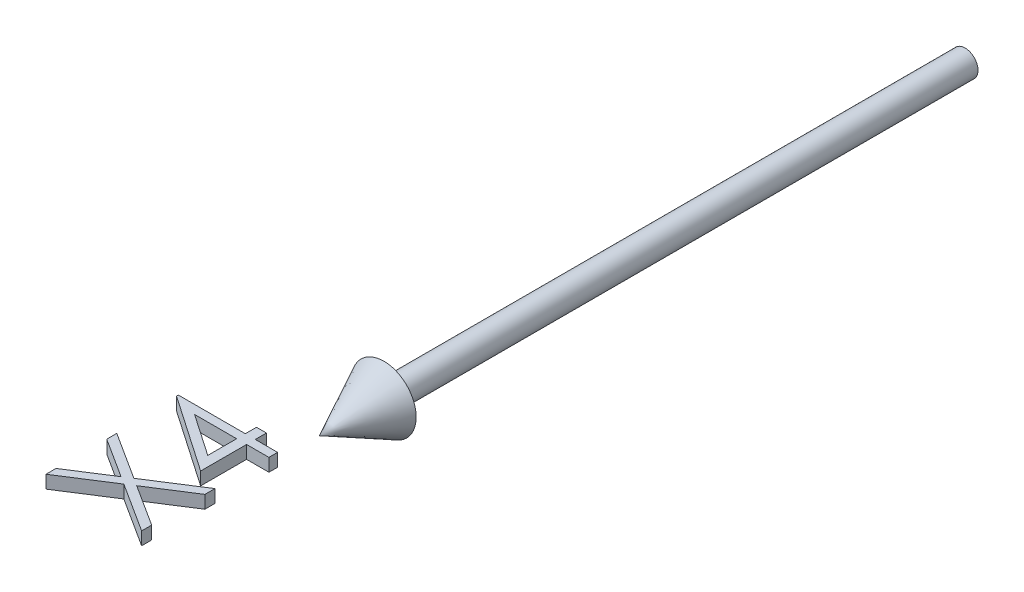
SolidWorks part; units mm, degrees
ref_plane "Front Plane" through (0, 0, 0) normal (0, 0, 1) x (1, 0, 0)
ref_plane "Top Plane" through (0, 0, 0) normal (0, 1, 0) x (1, 0, 0)
ref_plane "Right Plane" through (0, 0, 0) normal (1, 0, 0) x (0, 0, -1)
sketch "Sketch2" plane through (0, 0, 0) normal (0, 1, 0) x (1, 0, 0)
  line L0 (0, 41.95) -> (0, -114.4521) construction
  line L1 (-36.8894, 0) -> (41.4965, 0) construction
  line L2 (0, -100) -> (5, -90)
  line L3 (5, -90) -> (2, -90)
  line L4 (2, -90) -> (2, 0)
  line L5 (2, 0) -> (0, 0)
  line L6 (0, 0) -> (0, -100)
  dimension "D1" = 100
  dimension "D2" = 2
  dimension "D3" = 10
  dimension "D4" = 5
revolve "Revolve1" add sketch "Sketch2" angle 360 about L0
sketch "Sketch3" plane through (0, 0, 0) normal (0, 1, 0) x (1, 0, 0)
  line L0 (0, -103.9528) -> (0, -147.2622) construction
  line L1 (-18.6107, -118.3811) -> (18.3141, -118.3811) construction
  text T0 "X4\r\n" font "Century Gothic" height 15
extrude "Boss-Extrude1" add sketch "Sketch3" against normal blind 1 and the other way blind 1 separate body
equation "\"frame_arrow_length\"=100"
equation "\"D1@Sketch2\"=\"frame_arrow_length\""
equation "\"frame_arrow_odA\"=4"
equation "\"D2@Sketch2\"=\"frame_arrow_odA\"/2"
equation "\"frame_arrow_head_od\"=5"
equation "\"D4@Sketch2\"=\"frame_arrow_head_od\""
equation "\"frame_arrow_head_length\"=10"
equation "\"D3@Sketch2\"=\"frame_arrow_head_length\""
equation "\"tvarobot_theta1\"=30"
equation "\"link0_ringA_odA\"= 40"
equation "\"link0_ringA_odB\"= 25"
equation "\"link0_ringA_id\"= 20"
equation "\"link0_ringA_thickness\"= (\"link0_ringA_odB\" - \"link0_ringA_id\")/2"
equation "\"link0_ringA_height\"= 3"
equation "\"link0_ringA_heightA\"= 1.5"
equation "\"link0_ringA_heightB\"=\"link0_ringA_height\"-\"link0_ringA_heightA\""
equation "\"link0_ringB_odA\"= 40"
equation "\"link0_ringB_odB\"= 29"
equation "\"link0_ringB_id\"= \"link0_shaftA_bearing_id\"+1"
equation "\"link0_ringB_thickness\"= (\"link0_ringB_odB\" - \"link0_ringB_id\")/2"
equation "\"link0_ringB_height\"= 3"
equation "\"link0_ringB_heightA\"= 1.5"
equation "\"link0_ringB_heightB\"=\"link0_ringB_height\"-\"link0_ringB_heightA\""
equation "\"link0_shaftA_bearing_od\"=27"
equation "\"link0_shaftA_bearing_id\"=20"
equation "\"link0_shaftA_thrust_bearing_od\"=35"
equation "\"link0_shaftA_thrust_bearing_id\"=20.04"
equation "\"link0_shaftA_retaining_ring_id\"=18.5"
equation "\"link0_shaftA_retaining_ring_groove_width\"=1.5"
equation "\"link0_shaftA_spline_length\"=8.0"
equation "\"link0_shaftA_spline_depth\"=1.0"
equation "\"link0_shaftA_spline_width\"=4.0"
equation "\"link0_shaftA_odA\"=\"link0_shaftA_bearing_id\""
equation "\"link0_shaftA_odB\"=35"
equation "\"link0_shaftA_odC\"=\"link0_shaftA_bearing_id\""
equation "\"link0_shaftA_odD\"=\"link0_shaftA_odC\"-2*\"link0_shaftA_spline_depth\""
equation "\"link0_shaftA_odE\"=\"link0_shaftA_bearing_id\""
equation "\"link0_shaftA_odF\"=\"link0_shaftA_odE\"-2*\"link0_shaftA_spline_depth\""
equation "\"link0_shaftA_idA\"=10"
equation "\"link0_shaftA_idB\"=6"
equation "\"link0_shaftA_length\"=39.5"
equation "\"link0_shaftA_lengthA\"=8.0"
equation "\"link0_shaftA_lengthB\"=12.0"
equation "\"link0_shaftA_lengthC\"=35.0"
equation "\"link0_shaftA_lengthD\"=39.0"
equation "\"link0_shaftA_lengthE\"=\"link0_shaftA_length\"-\"link0_shaftA_lengthD\""
equation "\"link0_shaftA_offsetX\"=11"
equation "\"link0_shaftA_offsetY\"=0"
equation "\"link0_shaftA_bolt_pattern_dia\"=14"
equation "\"link0_motor_center_dist\"=26"
equation "\"link0_46t_pulley_spline_length\"=8"
equation "\"link0_46t_pulley_spline_depth\"=\"link0_shaftA_spline_depth\"*1.025"
equation "\"link0_46t_pulley_spline_width\"=\"link0_shaftA_spline_width\"*1.05"
equation "\"link0_46t_pulley_idA\"=\"link0_shaftA_bearing_id\"*1.025"
equation "\"link0_46t_pulley_idB\"=\"link0_46t_pulley_idA\"-2*\"link0_46t_pulley_spline_depth\""
equation "\"link0_shaftB_spline_length\"=10"
equation "\"link0_shaftB_spline_depth\"=1.0"
equation "\"link0_shaftB_spline_width\"=1.25"
equation "\"link0_shaftB_length\"=7"
equation "\"link0_shaftB_lengthA\"=1.5"
equation "\"link0_shaftB_lengthB\"=2.75"
equation "\"link0_shaftB_odA\"=32"
equation "\"link0_shaftB_odB\"=22"
equation "\"link0_shaftB_odC\"=20"
equation "\"link0_shaftB_idA\"=10"
equation "\"link0_shaftB_bolt_diameter\"=19"
equation "\"link0_shaftB_bearing_od\"=27"
equation "\"link0_shaftB_bearing_id\"=20"
equation "\"link0_motor_length\"=46.5"
equation "\"link0_motor_width\"=28.5"
equation "\"link0_motor_height\"=34"
equation "\"link0_motor_offset\"=8"
equation "\"link0_shellA_thickness\"=2.5"
equation "\"link0_shellB_thickness\"=\"link0_shellA_thickness\""
equation "\"link0_plateA_shellA_height\"=48"
equation "\"link0_shellA_width\" =\"link0_plateA_width\""
equation "\"link0_shellA_height\" = \"link0_plateA_shellA_height\"-\"link0_plateA_height\""
equation "\"link0_shellA_length\" = \"link0_plateA_lengthB\" "
equation "\"link0_shellB_length\"=\"link0_shellA_length\""
equation "\"link0_shellA_radius\" = 0.375*25.4"
equation "\"link0_shellA_radiusA\"= \"link0_plateA_radiusA\""
equation "\"link0_shellA_radiusB\"= \"link0_plateA_radiusB\""
equation "\"link0_shellA_radiusC\"= 3"
equation "\"link0_postA_height\"=7"
equation "\"link0_postA_width\"=16"
equation "\"link0_postA_length\"=20"
equation "\"link0_postA_posX\"=22"
equation "\"link0_postA_posY\"=17.5"
equation "\"link0_postA_pocket_width\"=6.0"
equation "\"link0_postA_pocket_length\"=2.5"
equation "\"link0_postA_pocket_depth\"=9"
equation "\"link0_postA_pocket_posZ\"=10"
equation "\"link0_postB_height\"=7"
equation "\"link0_postB_width\"=16"
equation "\"link0_postB_length\"=20"
equation "\"link0_postB_posX\"=22"
equation "\"link0_postB_posY\"=17.5"
equation "\"link0_postB_id\"=3.0"
equation "\"link0_postB_pocket_width\"=6.0"
equation "\"link0_postB_pocket_length\"=2.5"
equation "\"link0_postB_pocket_depth\"=9"
equation "\"link0_postB_pocket_posZ\"=10"
equation "\"link0_postC_height\"=7"
equation "\"link0_postC_width\"=16"
equation "\"link0_postC_length\"=20"
equation "\"link0_postC_posX\"=22"
equation "\"link0_postC_posY\"=17.5"
equation "\"link0_postC_id\"=3.0"
equation "\"link0_postC_pocket_width\"=6.0"
equation "\"link0_postC_pocket_length\"=2.5"
equation "\"link0_postC_pocket_depth\"=9"
equation "\"link0_postC_pocket_posZ\"=10"
equation "\"link0_postD_height\"=7"
equation "\"link0_postD_width\"=16"
equation "\"link0_postD_length\"=20"
equation "\"link0_postD_posX\"=22"
equation "\"link0_postD_posY\"=17.5"
equation "\"link0_postD_id\"=3.0"
equation "\"link0_postD_pocket_width\"=6.0"
equation "\"link0_postD_pocket_length\"=3.0"
equation "\"link0_postD_pocket_depth\"=9"
equation "\"link0_postD_pocket_posZ\"=10"
equation "\"link0_postE_height\"=5"
equation "\"link0_postE_width\"=16"
equation "\"link0_postE_length\"=\"link0_plateE_lengthA\"-\"link0_lip_height\""
equation "\"link0_postE_posZ\"=22"
equation "\"link0_postE_posX\"=17.5"
equation "\"link0_postE_posY\"=22"
equation "\"link0_postE_id\"=3.0"
equation "\"link0_postE_cbore_id\"=6.5"
equation "\"link0_postE_hole_id\"=3"
equation "\"link0_postF_posZ\"=22"
equation "\"link0_postF_posX\"=17.5"
equation "\"link0_postF_posY\"=\"link0_plateB_lengthA\"+4"
equation "\"link0_postF_id\"=3.0"
equation "\"link0_postF_cbore_id\"=6.5"
equation "\"link0_postF_hole_id\"=3"
equation "\"link0_postG_posZ\"=22"
equation "\"link0_postG_posX\"=17.5"
equation "\"link0_postG_posY\"=\"link0_plateB_lengthA\"+12"
equation "\"link0_postG_id\"=3.0"
equation "\"link0_postG_cbore_id\"=6.5"
equation "\"link0_postG_hole_id\"=3"
equation "\"link0_postHIJ_posY\"=6"
equation "\"link0_postH_posX\"=28"
equation "\"link0_postH_posY\"=20"
equation "\"link0_postH_posZ\"=20"
equation "\"link0_postH_length\"=10"
equation "\"link0_postI_posX\"=28"
equation "\"link0_postI_posY\"=20"
equation "\"link0_postI_posZ\"=135"
equation "\"link0_postI_length\"=10"
equation "\"link0_postJ_posX\"=28"
equation "\"link0_postJ_posY\"=20"
equation "\"link0_postJ_posZ\"=175"
equation "\"link0_postJ_length\"=10"
equation "\"link0_postK_posX\"=28"
equation "\"link0_postK_posY\"=20"
equation "\"link0_postK_posZ\"=175"
equation "\"link0_postK_length\"=10"
equation "\"link0_postL_posX\"=28"
equation "\"link0_postL_posY\"=20"
equation "\"link0_postL_posZ\"=135"
equation "\"link0_postL_length\"=10"
equation "\"link0_postM_posX\"=28"
equation "\"link0_postM_posY\"=20"
equation "\"link0_postM_posZ\"=35"
equation "\"link0_postM_length\"=10"
equation "\"link0_plateA_lengthA\"=30"
equation "\"link0_plateA_lengthB\"=150"
equation "\"link0_plateA_lengthC\"=30"
equation "\"link0_plateA_length\"=\"link0_plateA_lengthA\"+\"link0_plateA_lengthB\"+\"link0_plateA_lengthC\""
equation "\"link0_plateA_width\"=  68"
equation "\"link0_plateA_height\"= \"link0_plateA_radiusA\""
equation "\"link0_plateA_thickness\"=\"link0_shellA_thickness\""
equation "\"link0_plateA_radius\"= 9.5"
equation "\"link0_plateA_radiusA\"= 18"
equation "\"link0_plateA_radiusB\"= 18"
equation "\"link0_plateA_radiusC\"= 3"
equation "\"link0_plateB_length\"= 40"
equation "\"link0_plateB_width\"= \"link0_plateA_width\"*1.005"
equation "\"link0_plateB_height\"= \"link0_plateA_shellA_height\"*1.005"
equation "\"link0_plateB_lengthA\"=\"link0_lip_height\"+\"link0_plateD_thickness\"+\"link0_motor_mount_thickness\""
equation "\"link0_plateB_lengthB\"=\"link0_plateB_height\"-\"link0_plateB_lengthA\""
equation "\"link0_plateB_radiusA\"= \"link0_plateA_radiusA\""
equation "\"link0_plateB_radiusB\"= \"link0_plateA_radiusB\""
equation "\"link0_plateB_radiusC\"= 3"
equation "\"link0_plateB_idA\"=\"link0_shaftA_odC\"+1"
equation "\"link0_plateB_idB\"=\"link0_shaftA_bearing_od\"-2"
equation "\"link0_plateB_idC\"=\"link0_shaftA_bearing_od\"*1.005"
equation "\"link0_plateB_idD\"=\"link0_shaftA_thrust_bearing_od\"+1 "
equation "\"link0_plateB_depthA\"=1.0"
equation "\"link0_plateB_depthB\"=2.0"
equation "\"link0_plateB_depthC\"=8"
equation "\"link0_plateB_depthD\"=\"link0_plateB_length\"-\"link0_lip_height\"-\"link0_plateD_thickness\" "
equation "\"link0_plateC_length\"=\"link0_plateB_length\""
equation "\"link0_plateC_width\"= \"link0_plateB_width\""
equation "\"link0_plateC_height\"= .1*25.4"
equation "\"link0_plateA_hole_od\" = 0.1*25.4"
equation "\"link0_plateA_hole_delx\" = 0.5*25.4"
equation "\"link0_plateA_hole_delz\" = 0.75*25.4"
equation "\"link0_plateA_hole_offx\" = 0.0*25.4"
equation "\"link0_plateA_hole_offz\" = \"link0_plateA_length\"/2"
equation "\"link0_plateB_hole_od\" = 0.1*25.4"
equation "\"link0_plateB_hole_delx\"= 0.75*25.4"
equation "\"link0_plateB_hole_delz\"= 0.75*25.4"
equation "\"link0_plateB_hole_offx\"= 0.0*25.4"
equation "\"link0_plateB_hole_offz\"= 0.0*25.4"
equation "\"link0_plateC_hole_od\"= 0.1*25.4"
equation "\"link0_plateC_hole_delx\"= 0.75*25.4"
equation "\"link0_plateC_hole_delz\"= 0.75*25.4"
equation "\"link0_plateC_hole_offx\"= 0.0*25.4"
equation "\"link0_plateC_hole_offz\"= 0.0*25.4"
equation "\"link0_plateD_height\"=\"link0_plateB_height\"-2*\"link0_shellA_thickness\""
equation "\"link0_plateD_width\"=\"link0_plateB_width\"-2*\"link0_shellA_thickness\""
equation "\"link0_plateD_thickness\"=10"
equation "\"link0_plateD_radiusA\"=\"link0_plateB_radiusA\"-\"link0_shellA_thickness\""
equation "\"link0_plateD_odA\"= .375*25.4"
equation "\"link0_plateD_odB\"= .375*25.4"
equation "\"link0_plateD_bearing_id\"=20"
equation "\"link0_plateD_bearing_od\"=27"
equation "\"link0_plateE_radiusA\"=\"link0_plateA_radiusA\""
equation "\"link0_plateE_radiusB\"=\"link0_plateA_radiusB\""
equation "\"link0_plateE_radiusC\"=8.0"
equation "\"link0_plateE_length\"=30"
equation "\"link0_plateE_lengthA\"=16"
equation "\"link0_plateE_height\"=\"link0_plateB_height\""
equation "\"link0_plateE_width\"=\"link0_plateB_width\""
equation "\"link0_plateE_odA\"=\"gantry_coupler_id\"*0.99"
equation "\"link0_plateE_idA\"=\"link0_plateE_odA\"-20.0"
equation "\"link0_plateE_spline_depth\"=\"link0_poleA_spline_depth\"*1.05"
equation "\"link0_plateE_spline_width\"=\"link0_poleA_spline_width\"*1.075"
equation "\"link0_plateE_spline_length\"=\"link0_poleA_spline_length\""
equation "\"link0_plateE_coupler_length\"=46"
equation "\"link0_lip_height\"=5.0"
equation "\"link0_lip_thickness\"=2.0"
equation "\"link0_motor_mount_thickness\"=8.0"
equation "\"link0_motor_mount_idA\"=22"
equation "\"link0_motor_mount_idB\"=\"link0_shaftB_bearing_od\"*1.005"
equation "\"link0_motor_mount_idC\"=\"link0_shaftB_bearing_od\"-2"
equation "\"link0_motor_mount_depthA\"=5.5"
equation "\"link0_motor_mount_height\"=\"link0_plateD_height\""
equation "\"link0_motor_mount_width\"=\"link0_plateD_width\""
equation "\"link0_motor_mountL_height\"=36"
equation "\"link0_motor_mountL_heightA\"=12"
equation "\"link0_motor_mountL_length\"=50"
equation "\"link0_motor_mountL_lengthA\"=36"
equation "\"gantry_coupler_od\"=25.4*2.0"
equation "\"gantry_coupler_id\"=1.645*25.4"
equation "\"gantry_coupler_offsetX\"=\"link0_plateE_width\"/2"
equation "\"link0_poleA_odA\"=20"
equation "\"link0_poleA_odB\"=36"
equation "\"link0_poleA_idA\"=\"link0_poleA_odA\"-2*\"link0_poleA_thickness\""
equation "\"link0_poleA_idB\"=(\"link0_plateE_idA\"/2+1.5*\"link0_lip_thickness\")*1.04"
equation "\"link0_poleA_thickness\"=3.5"
equation "\"link0_poleA_length\"=100"
equation "\"link0_poleA_lengthA\"=18.5"
equation "\"link0_poleA_lengthB\"=80"
equation "\"link0_poleA_gasket_thickness\"=1.5"
equation "\"link0_poleA_spline_depth\"=1.0"
equation "\"link0_poleA_spline_width\"=4.0"
equation "\"link0_poleA_spline_length\"=10.0"
equation "\"link1_plateB_length\"=30"
equation "\"link1_lip_height\"=\"link0_lip_height\""
equation "\"link0_tension_plateA_width\"=12"
equation "\"link0_tension_plateA_lengthA\"=10.5"
equation "\"link0_tension_plateB_width\"=\"link0_tension_plateA_width\""
equation "\"link0_tension_plateB_lengthA\"=\"link0_tension_plateA_lengthA\""
equation "\"link0_tension_wheelA_posZ\"=7"
equation "\"link0_tension_wheelA_posX\"=\"link0_plateD_height\"/2-\"link0_tension_plateA_lengthA\""
equation "\"link0_m2_clear_hole_id\"=2.35"
equation "\"link0_m2_insert_hole_id\"=2.5"
equation "\"link0_m2_tap_hole_id\"=1.75"
equation "\"link0_m2_nut_socket_width\"=4.25"
equation "\"link0_m2_nut_socket_depth\"=2.5"
equation "\"link0_m2_cbore_id\"=3.75"
equation "\"link0_m2_cbore_depth\"=7"
equation "\"link0_m2_5_clear_hole_id\"=2.75"
equation "\"link0_m2_5_insert_hole_id\"=2.75"
equation "\"link0_m2_5_tap_hole_id\"=2.25"
equation "\"link0_m2_5_nut_socket_width\"=5.25"
equation "\"link0_m2_5_nut_socket_depth\"=2.5"
equation "\"link0_m2_5_cbore_id\"=4.75"
equation "\"link0_m2_5_cbore_depth\"=2.5"
equation "\"link0_m2_5_insert_access_length\"=6.0"
equation "\"link0_m2_5_insert_access_width\"=3.0"
equation "\"link0_m3_clear_hole_id\"=3.25"
equation "\"link0_m3_insert_hole_id\"=3"
equation "\"link0_m3_tap_hole_id\"=2.75"
equation "\"link0_m3_nut_socket_width\"=5.75"
equation "\"link0_m3_nut_socket_depth\"=4.0"
equation "\"link0_m3_cbore_id\"=5.75"
equation "\"link0_m3_cbore_depth\"=3.5"
equation "\"link0_m3_insert_access_length\"=4.5"
equation "\"link0_m3_insert_access_width\"=3.5"
equation "\"link0_rpi_mount_height\"=6"
equation "\"link0_rpi_mount_width\"=49"
equation "\"link0_rpi_mount_length\"=58"
equation "\"link0_rpi_mount_post_od\"=6"
equation "\"link0_rpi_mount_posZ\"=72"
equation "\"link0_rpi_mount_posX\"=11.5"
equation "\"link0_mcu_mount_height\"=5"
equation "\"link0_mcu_mount_width\"=49"
equation "\"link0_mcu_mount_length\"=58"
equation "\"link0_mcu_mount_post_od\"=6"
equation "\"link0_mcu_mount_posZ\"=164"
equation "\"link0_mcu_mount_posX\"=4"
equation "\"link0_pwr_mount_height\"=4"
equation "\"link0_pwr_mount_width\"=15.75"
equation "\"link0_pwr_mount_length\"=75.75"
equation "\"link0_pwr_mount_post_od\"=6"
equation "\"link0_pwr_mount_posZ\"=75"
equation "\"link0_pwr_mount_posX\"=16"
equation "\"link0_pwr_board_height\"=6"
equation "\"link0_pwr_board_width\"=21"
equation "\"link0_pwr_board_length\"=80"
